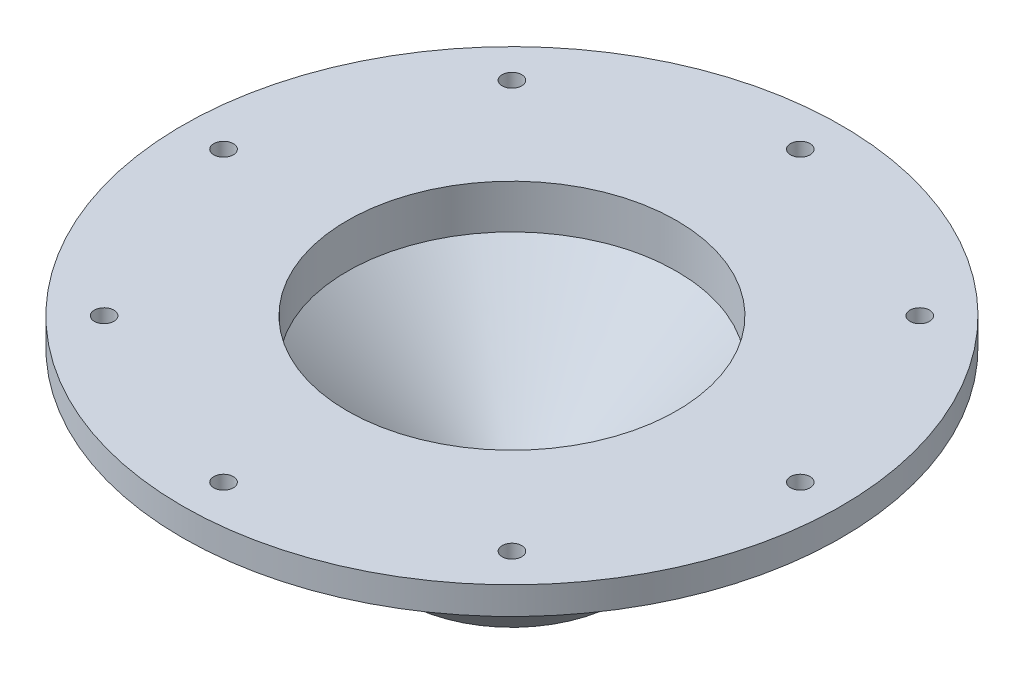
SolidWorks part; units mm, degrees
ref_plane "Front Plane" through (0, 0, 0) normal (0, 0, 1) x (1, 0, 0)
ref_plane "Top Plane" through (0, 0, 0) normal (0, 1, 0) x (1, 0, 0)
ref_plane "Right Plane" through (0, 0, 0) normal (1, 0, 0) x (0, 0, -1)
sketch "Sketch1" plane through (0, 0, 0) normal (0, 1, 0) x (1, 0, 0)
  circle A0 centre (0, 0) radius 38.1
  dimension "D1" = 76.2
extrude "Boss-Extrude1" add sketch "Sketch1" along normal blind 3.175
hole_wizard "Tap Drill for #4-40 Tap1" positions "Sketch3" profile "Sketch4" hole size "#4-40" standard "ANSI Inch" end condition through all
sketch "Sketch3" plane through (0, 0, 0) normal (0, -1, 0) x (-1, 0, 0)
  point P0 (0, -33.3375)
  dimension "D1" = 33.3375
sketch "Sketch4" plane through (0, 0, 33.3375) normal (1, 0, 0) x (0, 0, -1)
  line L0 (0, 0) -> (0, 3.175)
  line L1 (0, 3.175) -> (1.1303, 3.175)
  line L2 (1.1303, 3.175) -> (1.1303, 0)
  line L5 (1.1303, 0) -> (0, 0)
  line L11 (0, -6.35) -> (0, 107.95) construction
  dimension "Thru Hole Dia." = 2.2606
  dimension "Thru Hole Depth" = 3.175
pattern_circular "CirPattern1" count 8 over 360 about axis through (0, 0, 0) along (0, 1, 0) of "Tap Drill for #4-40 Tap1"
sketch "Sketch5" plane through (0, 0, 0) normal (0, -1, 0) x (1, 0, 0)
  circle A0 centre (0, 0) radius 25.4
  dimension "D1" = 50.8
extrude "Boss-Extrude2" add sketch "Sketch5" along normal blind 19.05
sketch "Sketch6" plane through (0, -19.05, 0) normal (0, -1, 0) x (1, 0, 0)
  circle A0 centre (0, 0) radius 4.7625
  dimension "D1" = 9.525
extrude "Cut-Extrude1" cut sketch "Sketch6" against normal through all both and the other way through all
sketch "Sketch7" plane through (0, 3.175, 0) normal (0, 1, 0) x (1, 0, 0)
  circle A0 centre (0, 0) radius 19.05
  dimension "D1" = 38.1
extrude "Cut-Extrude2" cut sketch "Sketch7" against normal blind 5.08
sketch "Sketch8" plane through (0, -1.905, 0) normal (0, 1, 0) x (1, 0, 0)
  circle A0 centre (0, 0) radius 19.05
  circle A1 centre (0, 0) radius 19.05 construction
  dimension "D1" = 0
ref_plane "Plane1" through (0, -15.875, 0) normal (0, -1, 0) x (-1, 0, 0)
sketch "Sketch9" plane through (0, -15.875, 0) normal (0, -1, 0) x (-1, 0, 0)
  circle A0 centre (0, 0) radius 4.7625
  circle A1 centre (0, 0) radius 4.7625 construction
  dimension "D1" = 0
loft "Cut-Loft1" cut profiles "Sketch8", "Sketch9" connector at (0, -1.905, 19.05) connector at (-1.301, -15.875, 4.5814)
chamfer "Chamfer1" distance 12.7 angle 45 1 edges at (0, -19.05, -25.4)
chamfer "Chamfer2" distance 0.127 angle 45 1 edges at (0, 0, 25.4)
